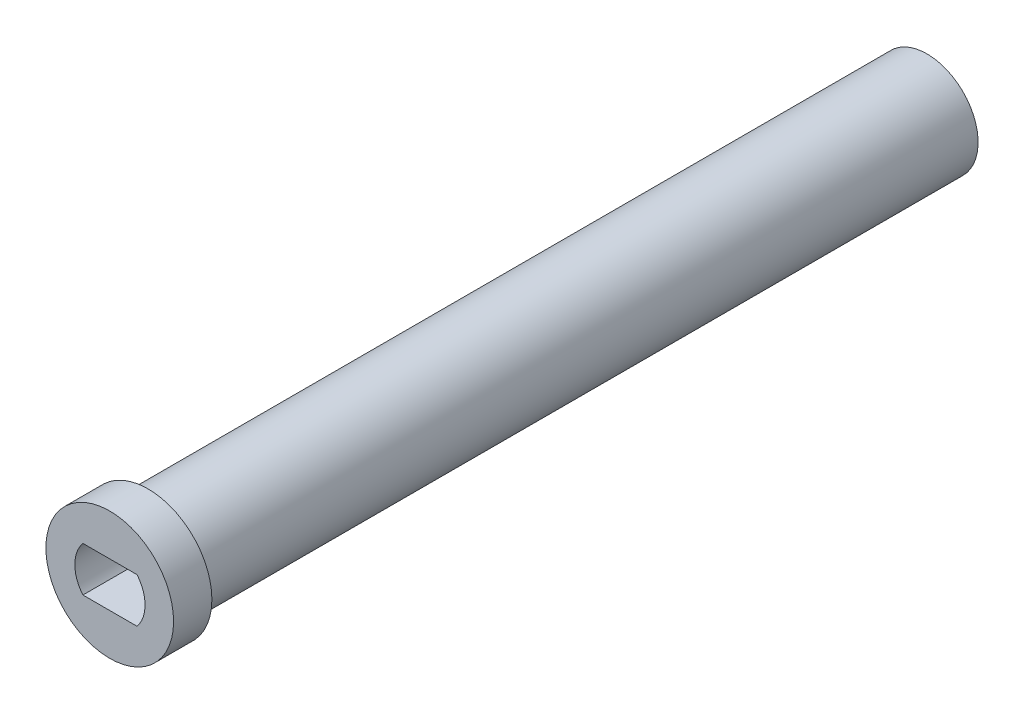
SolidWorks part; units mm, degrees
ref_plane "Front Plane" through (0, 0, 0) normal (0, 0, 1) x (1, 0, 0)
ref_plane "Top Plane" through (0, 0, 0) normal (0, 1, 0) x (1, 0, 0)
ref_plane "Right Plane" through (0, 0, 0) normal (1, 0, 0) x (0, 0, -1)
sketch "Sketch1" plane through (0, 0, 0) normal (0, 0, 1) x (1, 0, 0)
  line L0 (-2.1006, 1.75) -> (2.1421, 1.75)
  line L1 (-2.1006, -1.75) -> (2.1421, -1.75)
  arc A1 (2.1421, 1.75) -> (2.1421, -1.75) centre (0, 0) cw
  arc A2 (-2.1006, -1.75) -> (-2.1006, 1.75) centre (0.0037, 0) cw
  circle A3 centre (0, 0) radius 4
extrude "Boss-Extrude1" add sketch "Sketch1" along normal blind 40
sketch "Sketch2" plane through (0, 0, 40) normal (0, 0, 1) x (1, 0, 0)
  circle A2 centre (0, 0) radius 5
  circle A3 centre (0, 0) radius 5
  dimension "D1" = 1
extrude "Boss-Extrude2" add sketch "Sketch2" against normal blind 3
extrude "Cut-Extrude1" cut sketch "Sketch1<2>" against normal blind 3 and the other way blind 43 contours A2 L1 A1 L0 region at (0.0175, 0, 0)
sketch "Sketch1<2>" plane through (0, 0, 0) normal (0, 0, 1) x (1, 0, 0) same geometry as "Sketch1"
extrude "Boss-Extrude3" add sketch "Sketch1<3>" along normal blind 23 contours A3
sketch "Sketch1<3>" plane through (0, 0, 0) normal (0, 0, 1) x (1, 0, 0) same geometry as "Sketch1"
sketch "Sketch3" plane through (0, 0, 0) normal (0, 0, -1) x (-1, 0, 0)
  circle A0 centre (0, 0) radius 4
extrude "Boss-Extrude4" add sketch "Sketch3" along normal blind 24
